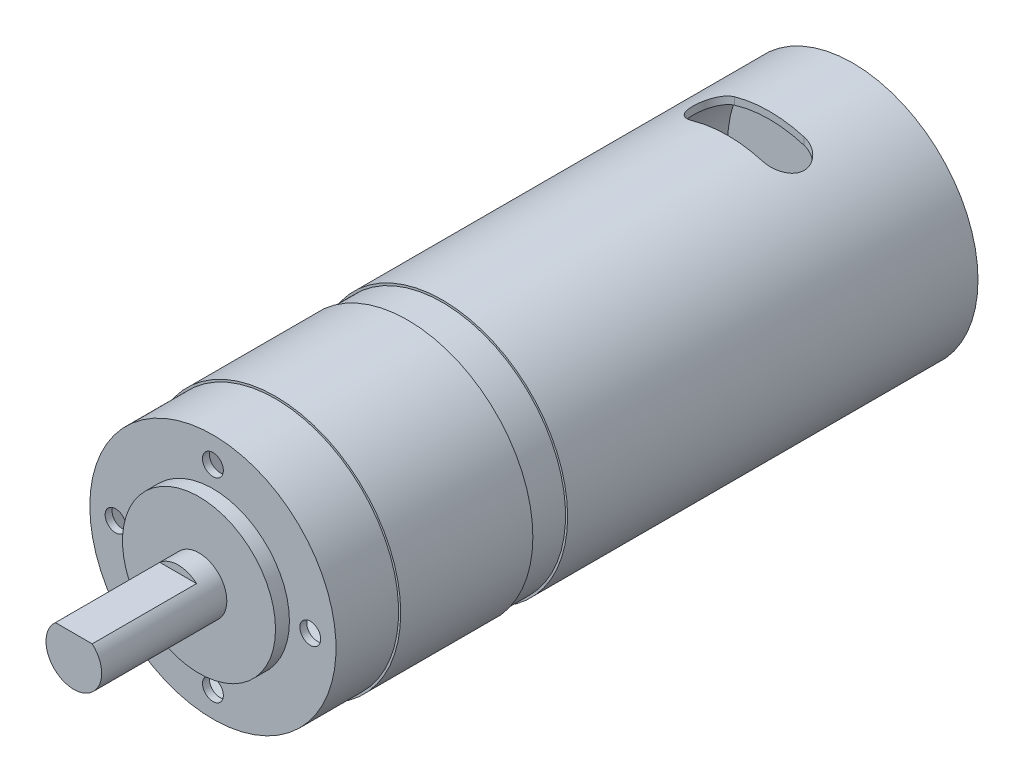
SolidWorks part; units mm, degrees
ref_plane "前视基准面" through (0, 0, 0) normal (0, 0, 1) x (1, 0, 0)
ref_plane "上视基准面" through (0, 0, 0) normal (0, 1, 0) x (1, 0, 0)
ref_plane "右视基准面" through (0, 0, 0) normal (1, 0, 0) x (0, 0, -1)
sketch "草图1" plane through (0, 0, 0) normal (0, 0, 1) x (1, 0, 0)
  circle A0 centre (0, 0) radius 18
  dimension "D1" = 36
extrude "凸台-拉伸1" add sketch "草图1" along normal blind 92
ref_plane "基准面1" through (0, 18, 0) normal (0, 1, 0) x (1, 0, 0)
sketch "草图7" plane through (0, 18, 0) normal (0, 1, 0) x (1, 0, 0)
  line L0 (0, 0) -> (0, -15)
  line L1 (-5, -15) -> (5, -15)
  line L2 (5, -15) -> (-5, -15) construction
  line L3 (5, -18) -> (-5, -18)
  line L4 (5, -12) -> (-5, -12)
  arc A0 (5, -18) -> (5, -12) centre (5, -15) ccw
  arc A1 (-5, -12) -> (-5, -18) centre (-5, -15) ccw
  point P5 (0, -15)
  dimension "D1" = 15
  dimension "D2" = 5
extrude "切除-拉伸2" cut sketch "草图7" against normal blind 36 contours L4 A1 L3 A0 region at (0, 18, 17.8291)
shell "抽壳8" thickness 1 removed face at (-6.4802, 0, 15) removed face at (6.4802, 0, 15) removed face at (0, 0, 18) removed face at (0, 0, 12)
sketch "草图2" plane through (0, 0, 92) normal (0, 0, 1) x (1, 0, 0)
  circle A0 centre (0, 0) radius 11
  dimension "D1" = 22
extrude "凸台-拉伸2" add sketch "草图2" along normal blind 2
sketch "草图3" plane through (0, 0, 94) normal (0, 0, 1) x (1, 0, 0)
  circle A0 centre (0, 0) radius 4
  dimension "D1" = 8
extrude "凸台-拉伸3" add sketch "草图3" along normal blind 18
sketch "草图4" plane through (0, 0, 112) normal (0, 0, 1) x (1, 0, 0)
  line L0 (0, 4) -> (0, 3)
  line L1 (-2.6458, 3) -> (2.6458, 3)
  circle A0 centre (0, 0) radius 4
  circle M1 centre (0, 0) radius 4
  dimension "D2" = 8
  dimension "D1" = 1
extrude "切除-拉伸1" cut sketch "草图4" against normal blind 15 contours L0 L1 M1 | L1 L0 M1 region at (1.0111, 3.4046, 112) region at (-1.0111, 3.4046, 112)
sketch "草图5" plane through (0, 0, 0) normal (0, 0, -1) x (-1, 0, 0)
  circle A0 centre (0, 0) radius 5
  dimension "D1" = 10
extrude "凸台-拉伸4" add sketch "草图5" along normal blind 3
sketch "草图6" plane through (0, 0, -3) normal (0, 0, -1) x (-1, 0, 0)
  circle A0 centre (0, 0) radius 1.5
  dimension "D1" = 3
extrude "凸台-拉伸5" add sketch "草图6" along normal blind 1
fillet "圆角1" radius 1 2 edges at (-1.5, 0, -4) (-5, 0, -3)
sketch "草图8" plane through (0, 0, 92) normal (0, 0, 1) x (1, 0, 0)
  circle A0 centre (0, 0) radius 14
  circle A1 centre (14, 0) radius 1.5
  circle A2 centre (0, -14) radius 1.5
  circle A3 centre (-14, 0) radius 1.5
  circle A4 centre (0, 14) radius 1.5
  point P14 (0, 0)
  dimension "D1" = 28
  dimension "D2" = 3
  dimension "D3" = 4
extrude "切除-拉伸3" cut sketch "草图8" against normal blind 5 contours A0 A4 | A0 A4 | A0 A1 | A0 A1 | A3 | A2 region at (13.3491, 0, 92) region at (14.6219, 0, 92) region at (0, 13.3491, 92) region at (0, 14.6219, 92)
sketch "草图9" plane through (0, 0, 0) normal (0, 1, 0) x (1, 0, 0)
  line L0 (0, 0) -> (0, -112) construction
  line L1 (-4, -112) -> (4, -112) construction
  line L2 (-18, -92) -> (18, -92) construction
  line L3 (18, -92) -> (17.7, -92)
  line L4 (18, -92) -> (18, -83)
  line L5 (18, -83) -> (17.7, -83)
  line L6 (17.7, -92) -> (17.7, -83)
  line L8 (18, -64) -> (17.7, -64)
  line L9 (18, -64) -> (18, -59)
  line L10 (18, -59) -> (17.7, -59)
  line L11 (17.7, -64) -> (17.7, -59)
  dimension "D1" = 0.3
  dimension "D2" = 0.3
  dimension "D3" = 9
  dimension "D4" = 19
  dimension "D5" = 5
revolve "切除-旋转1" cut sketch "草图9" angle 360 about L0
